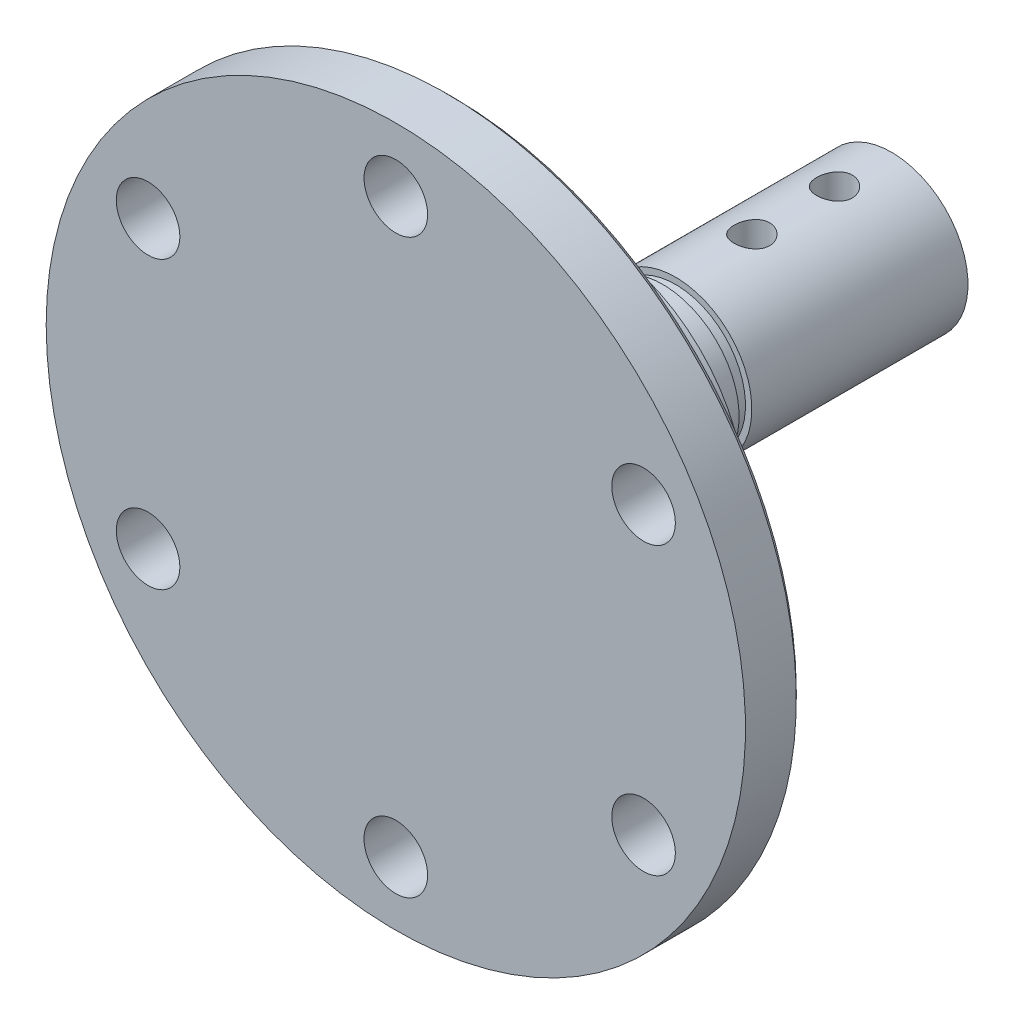
SolidWorks part; units mm, degrees
ref_plane "前视基准面" through (0, 0, 0) normal (0, 0, 1) x (1, 0, 0)
ref_plane "上视基准面" through (0, 0, 0) normal (0, 1, 0) x (1, 0, 0)
ref_plane "右视基准面" through (0, 0, 0) normal (1, 0, 0) x (0, 0, -1)
sketch "草图1" plane through (0, 0, 0) normal (0, 1, 0) x (1, 0, 0)
  line L0 (-6, 20.0001) -> (-6, 36.0001)
  line L1 (-6, 36.0001) -> (0, 36.0001)
  line L2 (0, 36.0001) -> (0, 30.0001)
  line L4 (-6, 13.0001) -> (-9, 13.0001)
  line L5 (-9, 13.0001) -> (-9, 6.5)
  line L23 (-6, 20.0001) -> (-6, 19.0001)
  line L24 (-6, 19.0001) -> (-5.5, 19.0001)
  line L25 (-5.5, 19.0001) -> (-5.5, 18.0001)
  line L26 (-5.5, 18.0001) -> (-6, 18.0001)
  line L27 (-6, 18.0001) -> (-6, 13.0001)
  line L30 (-9, 1.5) -> (-9, 6.5)
  line L31 (-9, 1.5) -> (-27, 1.5)
  line L32 (-27, 1.5) -> (-27.5, 1)
  line L33 (-27.5, 1) -> (-27.5, -3)
  line L34 (-27.5, -3) -> (-9.75, -3)
  line L35 (-9.75, -3) -> (-9.75, -33.2999)
  line L36 (-9.75, -33.2999) -> (-9.2499, -33.8)
  line L37 (-9.2499, -33.8) -> (0, -33.8)
  line L38 (0, 30.0001) -> (0, -33.8)
revolve "旋转1" add sketch "草图1" angle 360 about L38
sketch "草图2" plane through (0, 0, 33.8) normal (0, 0, 1) x (1, 0, 0)
  circle A0 centre (0, 0) radius 6.5
  dimension "D1" = 13
extrude "切除-拉伸1" cut sketch "草图2" against normal blind 28
chamfer "倒角1" distance 0.5 angle 45 1 edges at (6.5, 0, 33.8)
sketch "草图3" plane through (0, 0, -1.5) normal (0, 0, -1) x (-1, 0, 0)
  circle A0 centre (0, 0) radius 22.5 construction
  circle A1 centre (0, 22.5) radius 2.5
  circle A2 centre (19.4856, 11.25) radius 2.5
  circle A3 centre (19.4856, -11.25) radius 2.5
  circle A4 centre (0, -22.5) radius 2.5
  circle A5 centre (-19.4856, -11.25) radius 2.5
  circle A6 centre (-19.4856, 11.25) radius 2.5
  point P17 (0, 0)
  dimension "D1" = 45
  dimension "D2" = 6
extrude "切除-拉伸2" cut sketch "草图3" against normal blind 23
sketch "草图4" plane through (0, 0, -36.0001) normal (0, 0, -1) x (-1, 0, 0)
  circle A0 centre (0, 0) radius 3.1
  dimension "D1" = 6.2
extrude "切除-拉伸3" cut sketch "草图4" against normal blind 20
sketch "草图5" plane through (0, 0, 33.8) normal (0, 0, 1) x (1, 0, 0)
  circle A0 centre (0, 0) radius 16.0175
extrude "切除-拉伸4" cut sketch "草图5" against normal up to surface (30.8 mm away) up to face at (21.9856, 11.25, 3)
sketch "草图6" plane through (0, 0, -13.0001) normal (0, 0, -1) x (-1, 0, 0)
  circle A0 centre (0, 0) radius 9
  circle A1 centre (0, 0) radius 12
extrude "凸台-拉伸1" add sketch "草图6" against normal blind 13
sketch "草图7" plane through (0, 0, -13.0001) normal (0, 0, -1) x (-1, 0, 0)
  circle A1 centre (0, 0) radius 9
  circle A2 centre (0, 0) radius 12
extrude "切除-拉伸5" cut sketch "草图7" against normal blind 0.5
chamfer "倒角2" distance 0.5 angle 45 1 edges at (-9, 0, -12.5001)
sketch "草图8" plane through (0, 0, 0) normal (0, 1, 0) x (1, 0, 0)
  line L0 (0, 36.0001) -> (0, 19.0001) construction
  line L1 (6, 36.0001) -> (-6, 36.0001) construction
  line L2 (-5.5, 19.0001) -> (5.5, 19.0001) construction
  circle A0 centre (0, 31.5001) radius 1.4
  circle A1 centre (0, 25.0001) radius 1.4
  dimension "D1" = 4.5
  dimension "D2" = 6.5
extrude "切除-拉伸6" cut sketch "草图8" against normal blind 30.5 and the other way blind 20.5
